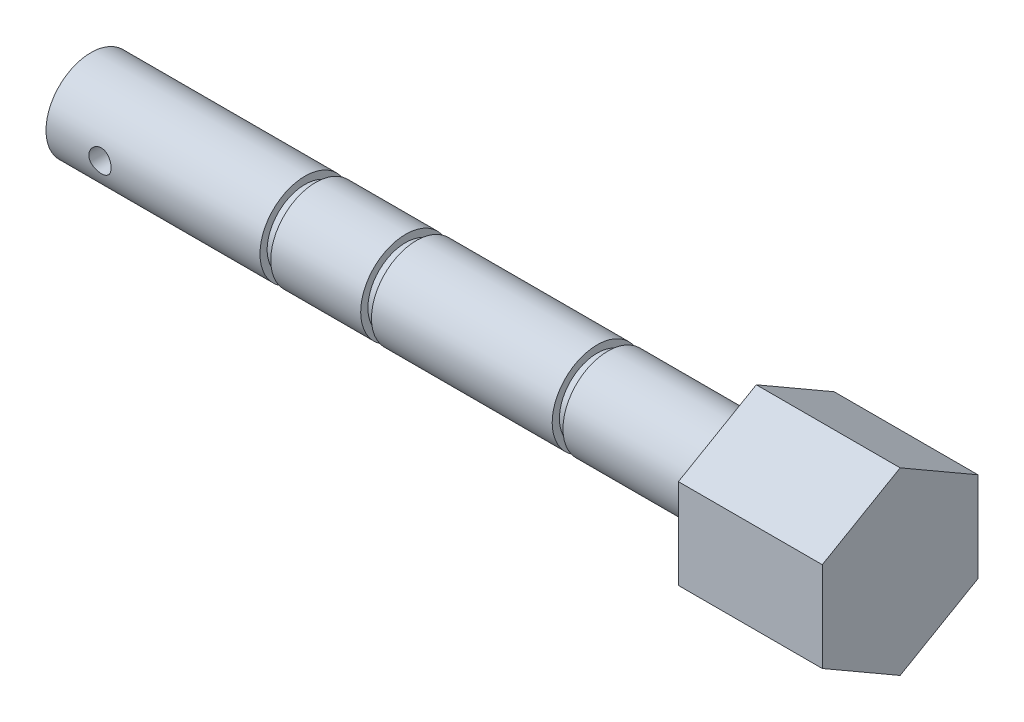
SolidWorks part; units mm, degrees
ref_plane "Front Plane" through (0, 0, 0) normal (0, 0, 1) x (1, 0, 0)
ref_plane "Top Plane" through (0, 0, 0) normal (0, 1, 0) x (1, 0, 0)
ref_plane "Right Plane" through (0, 0, 0) normal (1, 0, 0) x (0, 0, -1)
sketch "Sketch1" plane through (0, 0, 0) normal (1, 0, 0) x (0, 0, -1)
  circle A0 centre (0, 0) radius 3.175
extrude "Boss-Extrude2" add sketch "Sketch1" along normal blind 46.99 contours A0
sketch "Sketch2" plane through (46.99, 0, 0) normal (1, 0, 0) x (0, 0, -1)
  line L1 (-5.4993, 3.175) -> (-5.4993, -3.175)
  line L2 (-5.4993, -3.175) -> (0, -6.35)
  line L3 (0, -6.35) -> (5.4993, -3.175)
  line L4 (5.4993, -3.175) -> (5.4993, 3.175)
  line L5 (5.4993, 3.175) -> (0, 6.35)
  line L6 (0, 6.35) -> (-5.4993, 3.175)
  circle A0 centre (0, 0) radius 5.4993 construction
  dimension "D1" = 6.35
extrude "Boss-Extrude3" add sketch "Sketch2" along normal blind 10.16
sketch "Sketch3" plane through (0, 0, 0) normal (-1, 0, 0) x (0, 0, 1)
  circle A0 centre (0, 0) radius 1.778
  circle A1 centre (0, 0) radius 3.175
extrude "Cut-Extrude1" cut sketch "Sketch3" against normal blind 19.05
sketch "Sketch6" plane through (0, 0, 0) normal (-1, 0, 0) x (0, 0, 1)
  circle A0 centre (0, 0) radius 3.175
extrude "Boss-Extrude5" add sketch "Sketch6" against normal blind 49.022
sketch "Sketch7" plane through (0, 0, 0) normal (-1, 0, 0) x (0, 0, 1)
  line L1 (-0.4893, 0.7146) -> (-0.8635, -0.0664)
  line L2 (-0.8635, -0.0664) -> (-0.3742, -0.781)
  line L3 (-0.3742, -0.781) -> (0.4893, -0.7146)
  line L4 (0.4893, -0.7146) -> (0.8635, 0.0664)
  line L5 (0.8635, 0.0664) -> (0.3742, 0.781)
  line L6 (0.3742, 0.781) -> (-0.4893, 0.7146)
  circle A0 centre (0, 0) radius 0.75 construction
extrude "Cut-Extrude5" cut sketch "Sketch7" against normal blind 38.1
sketch "Sketch9" plane through (0, 0, 0) normal (-1, 0, 0) x (0, 0, 1)
  circle A0 centre (0, 0) radius 0.866
extrude "Cut-Extrude7" cut sketch "Sketch9" against normal blind 46.99 contours A0
sketch "Sketch10" plane through (0, 0, 5.4993) normal (0, 0, 1) x (1, 0, 0)
  line L0 (0, -3.175) -> (46.99, -3.175) construction
  circle A0 centre (3.81, 0) radius 0.7874
  dimension "D1" = 1.5748
  dimension "D2" = 3.81
  dimension "D3" = 3.175
extrude "Cut-Extrude8" cut sketch "Sketch10" against normal blind 5.334 contours A0
ref_plane "Plane1" through (36.5125, 0, 0) normal (-1, 0, 0) x (0, 0, 1)
sketch "Sketch11" plane through (36.5125, 0, 0) normal (-1, 0, 0) x (0, 0, 1)
  circle A0 centre (0, 0) radius 2.667
  circle A1 centre (0, 0) radius 3.175
  dimension "D1" = 5.334
  dimension "D2" = 6.35
extrude "Cut-Extrude9" cut sketch "Sketch11" along normal blind 0.762
ref_plane "Plane2" through (15.875, 0, 0) normal (-1, 0, 0) x (0, 0, 1)
sketch "Sketch12" plane through (15.875, 0, 0) normal (-1, 0, 0) x (0, 0, 1)
  circle A0 centre (0, 0) radius 2.667
  circle A1 centre (0, 0) radius 3.175
  dimension "D1" = 5.334
  dimension "D2" = 6.35
extrude "Cut-Extrude10" cut sketch "Sketch12" along normal blind 0.762
ref_plane "Plane3" through (22.987, 0, 0) normal (-1, 0, 0) x (0, 0, 1)
sketch "Sketch13" plane through (22.987, 0, 0) normal (-1, 0, 0) x (0, 0, 1)
  circle A0 centre (0, 0) radius 2.667
  circle A1 centre (0, 0) radius 3.175
  dimension "D1" = 5.334
  dimension "D2" = 6.35
extrude "Cut-Extrude12" cut sketch "Sketch13" along normal blind 0.762
